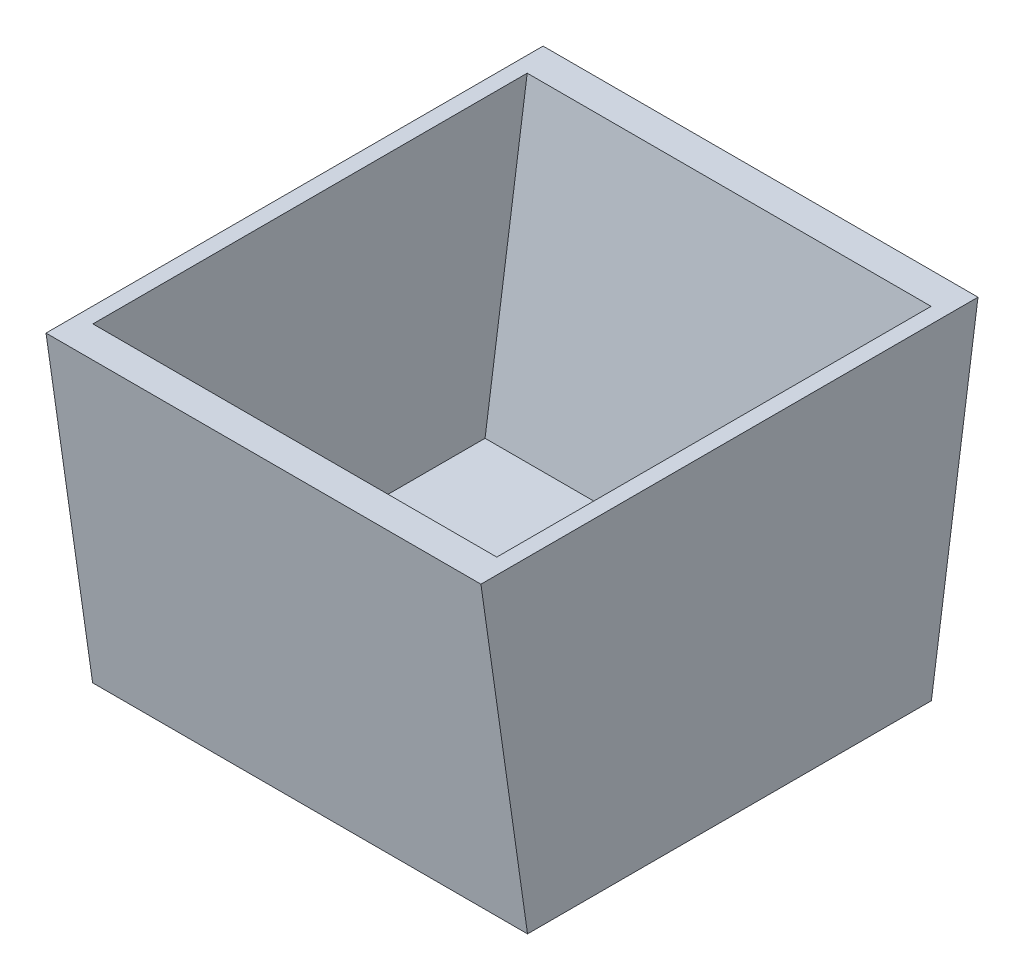
SolidWorks part; units mm, degrees
ref_plane "Front Plane" through (0, 0, 0) normal (0, 0, 1) x (1, 0, 0)
ref_plane "Top Plane" through (0, 0, 0) normal (0, 1, 0) x (1, 0, 0)
ref_plane "Right Plane" through (0, 0, 0) normal (1, 0, 0) x (0, 0, -1)
sketch "Sketch1" plane through (0, 0, 0) normal (0, 1, 0) x (1, 0, 0)
  line L1 (-177.8, 165.1) -> (177.8, 165.1)
  line L2 (-177.8, 165.1) -> (-177.8, -165.1)
  line L3 (-177.8, -165.1) -> (177.8, -165.1)
  line L4 (177.8, 165.1) -> (177.8, -165.1)
  line L5 (-177.8, 165.1) -> (177.8, -165.1) construction
  line L6 (-177.8, -165.1) -> (177.8, 165.1) construction
  point P0 (0, 0)
  dimension "D1" = 355.6
  dimension "D2" = 330.2
ref_plane "Plane1" through (0, 266.7, 0) normal (0, 1, 0) x (1, 0, 0)
sketch "Sketch2" plane through (0, 266.7, 0) normal (0, 1, 0) x (1, 0, 0)
  line L1 (-177.8, 203.2) -> (177.8, 203.2)
  line L2 (-177.8, 203.2) -> (-177.8, -203.2)
  line L3 (-177.8, -203.2) -> (177.8, -203.2)
  line L4 (177.8, 203.2) -> (177.8, -203.2)
  line L5 (-177.8, 203.2) -> (177.8, -203.2) construction
  line L6 (-177.8, -203.2) -> (177.8, 203.2) construction
  point P0 (0, 0)
  dimension "D1" = 406.4
  dimension "D2" = 355.6
loft "Loft1" add profiles "Sketch1", "Sketch2" connector at (177.8, 0, -165.1) connector at (177.8, 266.7, -203.2)
shell "Shell1" thickness 25.4 removed face at (0, 266.7, 0)
